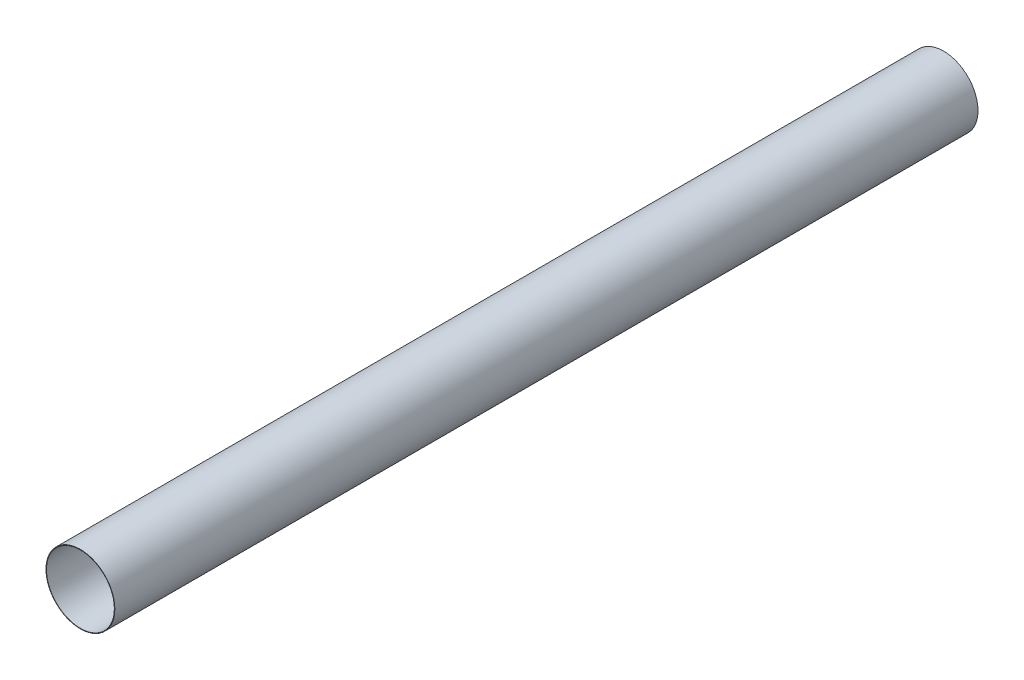
SolidWorks part; units mm, degrees
material "6061-T6 (SS)"
ref_plane "Front Plane" through (0, 0, 0) normal (0, 0, 1) x (1, 0, 0)
ref_plane "Top Plane" through (0, 0, 0) normal (0, 1, 0) x (1, 0, 0)
ref_plane "Right Plane" through (0, 0, 0) normal (1, 0, 0) x (0, 0, -1)
other "Center of Mass"
sketch "Sketch1" plane through (0, 0, 0) normal (0, 0, 1) x (1, 0, 0)
  circle A0 centre (0, 0) radius 71
  circle A1 centre (0, 0) radius 72
  dimension "D1" = 144
  dimension "D2" = 1
extrude "Boss-Extrude1" add sketch "Sketch1" along normal blind 1804
ref_plane "Mid-Plane" through (0, 0, 902) normal (0, 0, 1) x (1, 0, 0)
ref_axis "Axis1" through (0, 0, 1902.5) along (0, 0, -1)
ref_plane "Plane1" through (0, 0, 1834) normal (0, 0, 1) x (1, 0, 0)
